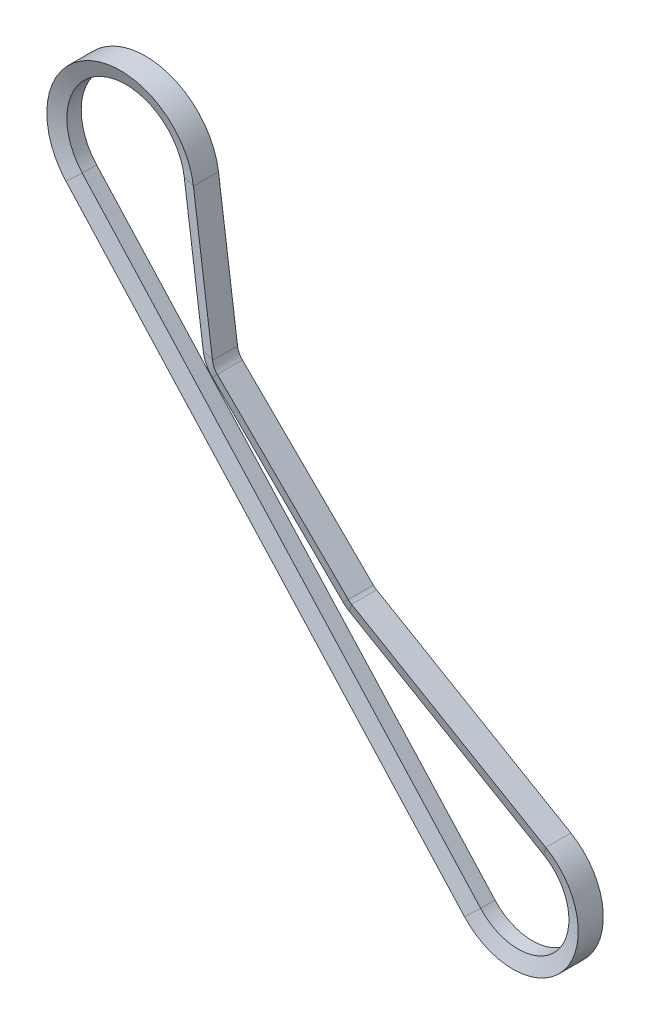
SolidWorks part; units mm, degrees
ref_plane "Front Plane" through (0, 0, 0) normal (0, 0, 1) x (1, 0, 0)
ref_plane "Top Plane" through (0, 0, 0) normal (0, 1, 0) x (1, 0, 0)
ref_plane "Right Plane" through (0, 0, 0) normal (1, 0, 0) x (0, 0, -1)
sketch "Sketch2" plane through (0, 0, 0) normal (0, 0, 1) x (1, 0, 0)
  line L0 (0, 0) -> (1, 0) construction
  line L1 (0, 0) -> (0, 1) construction
  line L12 (-18.3922, -16.7479) -> (-169.8664, 149.5975)
  line L14 (-121.4148, 172.191) -> (-114.1703, 118.463)
  line L15 (-112.3417, 114.796) -> (-62.5632, 65.5811)
  line L16 (-61.3014, 64.6136) -> (12.5461, 21.4793)
  arc A4 (-169.8664, 149.5975) -> (-121.4148, 172.191) centre (-149.1636, 168.4494) cw
  arc A7 (12.5461, 21.4793) -> (-18.3922, -16.7479) centre (0, 0) cw
  arc A8 (-114.1703, 118.463) -> (-112.3417, 114.796) centre (-107.8772, 119.3116) ccw
  arc A9 (-62.5632, 65.5811) -> (-61.3014, 64.6136) centre (-58.0987, 70.0968) ccw
ref_plane "Plane4" through (12.5461, 21.4793, 0) normal (0.8635, -0.5044, 0) x (-0.5044, -0.8635, 0)
sketch "Sketch3" plane through (12.5461, 21.4793, 0) normal (0.8635, -0.5044, 0) x (-0.5044, -0.8635, 0)
  line L0 (0, -4.7625) -> (0, 4.7625)
  line L1 (0, -4.7625) -> (5.588, -2.7286)
  line L2 (5.588, -2.7286) -> (5.588, 2.7286)
  line L3 (5.588, 2.7286) -> (0, 4.7625)
  line L4 (0, 0) -> (5.588, 0) construction
  dimension "D1" = 9.525
  dimension "D2" = 5.588
  dimension "D3" = 40
sweep "Sweep1" add profiles "Sketch3" path "Sketch2"
